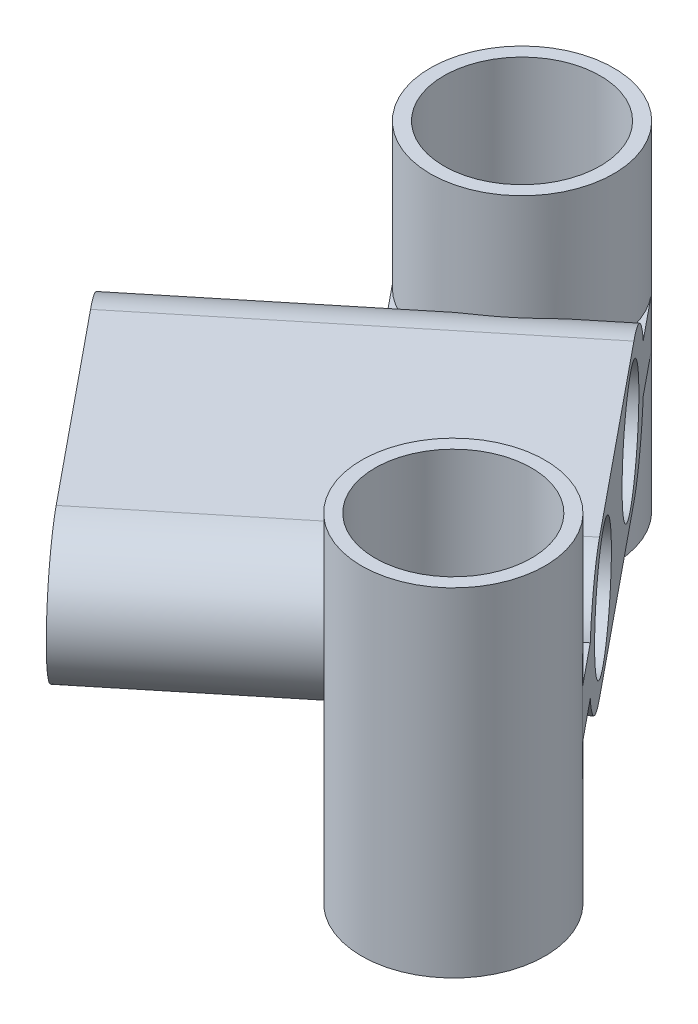
SolidWorks part; units mm, degrees
ref_plane "Front Plane" through (0, 0, 0) normal (0, 0, 1) x (1, 0, 0)
ref_plane "Top Plane" through (0, 0, 0) normal (0, 1, 0) x (1, 0, 0)
ref_plane "Right Plane" through (0, 0, 0) normal (1, 0, 0) x (0, 0, -1)
sketch "Sketch3" plane through (0, 0, 0) normal (0, 1, 0) x (1, 0, 0)
  line L0 (-10.5344, 25.8075) -> (21.0827, -12.927) construction
  line L1 (-3.1749, 31.8147) -> (28.4422, -6.9197)
  line L2 (-17.894, 19.8002) -> (13.7232, -18.9342)
  arc A4 (-3.1749, 31.8147) -> (-17.894, 19.8002) centre (-10.5344, 25.8075) ccw
  arc A5 (13.7232, -18.9342) -> (28.4422, -6.9197) centre (21.0827, -12.927) ccw
  point P8 (5.2741, 6.4402)
  dimension "D1" = 9.5
  dimension "D3" = 50
extrude "Boss-Extrude2" add sketch "Sketch3" along normal blind 5
sketch "Sketch4" plane through (0, 5, 0) normal (0, 1, 0) x (1, 0, 0)
  circle A0 centre (-10.5344, 25.8075) radius 9.5
  circle A1 centre (21.0827, -12.927) radius 9.5
  circle A2 centre (21.0827, -12.927) radius 8.1
  circle A3 centre (-10.5344, 25.8075) radius 8.1
  arc A5 (-3.1749, 31.8147) -> (-17.894, 19.8002) centre (-10.5344, 25.8075) ccw construction
  arc A6 (13.7232, -18.9342) -> (28.4422, -6.9197) centre (21.0827, -12.927) ccw construction
  dimension "D1" = 16.2
  dimension "D2" = 16.2
extrude "Boss-Extrude3" add sketch "Sketch4" along normal blind 15 and the other way blind 20
sketch "Sketch5" plane through (-1.0394, 0, 0.8484) normal (-0.7747, 0, 0.6323) x (0.6323, 0, 0.7747)
  line L0 (-14.1541, 2.5) -> (10.8459, 2.5) construction
  line L1 (-14.1541, 9.7169) -> (10.8459, 9.7169)
  line L2 (-14.1541, -4.7169) -> (10.8459, -4.7169)
  line L3 (-26.6541, 5) -> (-26.6541, 0) construction
  line L4 (-26.6541, 0) -> (23.3459, 0) construction
  line L5 (-26.6541, 5) -> (23.3459, 5) construction
  arc A0 (-14.1541, 9.7169) -> (-14.1541, -4.7169) centre (-14.1541, 2.5) ccw
  arc A1 (10.8459, -4.7169) -> (10.8459, 9.7169) centre (10.8459, 2.5) ccw
  circle A2 centre (-11.6541, 2.5) radius 6.1
  circle A3 centre (8.3459, 2.5) radius 6.1
  point P2 (-1.6541, 2.5)
  point P9 (-26.6541, 2.5)
  point P13 (-1.6541, 5)
  point P17 (0, 0)
  dimension "D1" = 12.2
  dimension "D2" = 20
  dimension "D3" = 10
  dimension "D4" = 25
extrude "Boss-Extrude4" add sketch "Sketch5" along normal blind 21 and the other way blind 19
sketch "Sketch6" plane through (-17.3079, 0, 14.1276) normal (-0.7747, 0, 0.6323) x (0.6323, 0, 0.7747)
  circle A0 centre (-11.6541, 2.5) radius 6.1
  circle A1 centre (8.3459, 2.5) radius 6.1
  circle A2 centre (-11.6541, 2.5) radius 6.1 construction
  circle A3 centre (8.3459, 2.5) radius 6.1 construction
  point P4 (0, 0)
extrude "Cut-Extrude2" cut sketch "Sketch6" against normal blind 41
